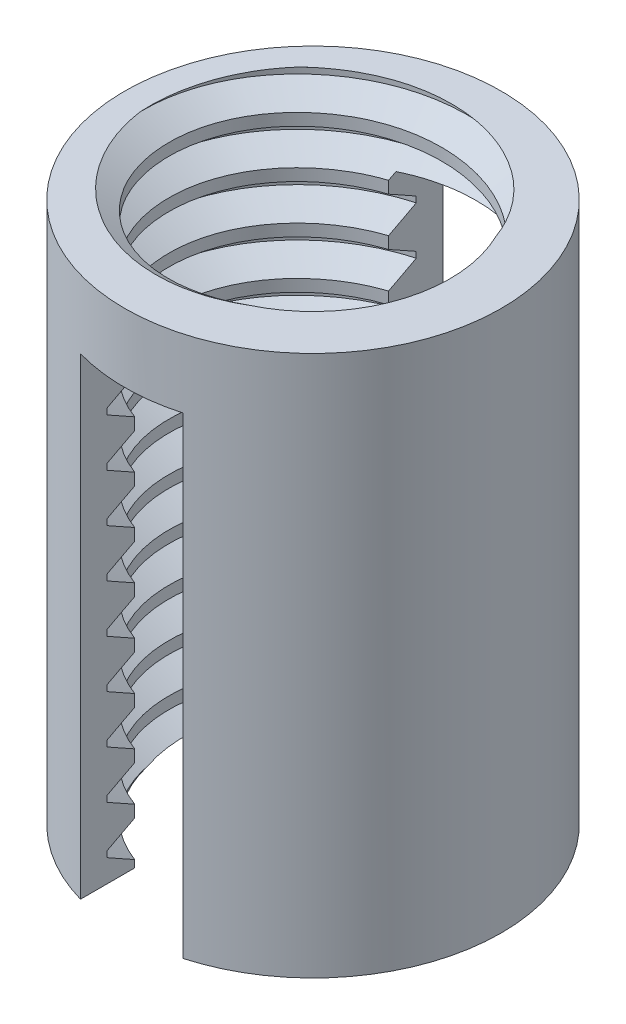
SolidWorks part; units mm, degrees
ref_plane "Front Plane" through (0, 0, 0) normal (0, 0, 1) x (1, 0, 0)
ref_plane "Top Plane" through (0, 0, 0) normal (0, 1, 0) x (1, 0, 0)
ref_plane "Right Plane" through (0, 0, 0) normal (1, 0, 0) x (0, 0, -1)
sketch "Sketch1" plane through (0, 0, 0) normal (0, 1, 0) x (1, 0, 0)
  circle A0 centre (0, 0) radius 2.75
  circle A1 centre (0, 0) radius 2
  dimension "D1" = 5.5
  dimension "D2" = 4
extrude "Boss-Extrude1" add sketch "Sketch1" along normal blind 7.9
sketch "Sketch2" plane through (0, 0, 0) normal (0, -1, 0) x (1, 0, 0)
  line L1 (-0.75, 2.75) -> (0.75, 2.75)
  line L2 (-0.75, 2.75) -> (-0.75, -2.75)
  line L3 (-0.75, -2.75) -> (0.75, -2.75)
  line L4 (0.75, 2.75) -> (0.75, -2.75)
  line L5 (-0.75, 2.75) -> (0.75, -2.75) construction
  line L6 (-0.75, -2.75) -> (0.75, 2.75) construction
  circle A0 centre (0, 0) radius 2.75 construction
  point P0 (0, 0)
  dimension "D1" = 1.5
extrude "Cut-Extrude1" cut sketch "Sketch2" against normal blind 6.9
thread "Thread1" pitch 0.7 start angle 0, offset 1, length 10, pitch 0.7, diameter 4
ref_plane "Plane1" through (-2, 8.9, 0) normal (0, 0, 1) x (-1, 0, 0)
sketch "Thread Profile1" plane through (-2, 8.9, 0) normal (0, 0, 1) x (-1, 0, 0)
  line L0 (0, 0) -> (0, 0.7) construction
  line L1 (0, 0) -> (0.3789, 0.2187)
  line L2 (0.3789, 0.2187) -> (0.3789, 0.3062)
  line L3 (0.3789, 0.3062) -> (0, 0.525)
  line L4 (0.3789, 0.2625) -> (0, 0.2625) construction
  line L11 (0, 0) -> (0, 0.525)
  point P2 (0, 0)
  dimension "Pitch" = 0.7
  dimension "Profile_Angle" = 60
  dimension "Profile_Land" = 0.0875
  dimension "Profile_Height" = 0.3789
